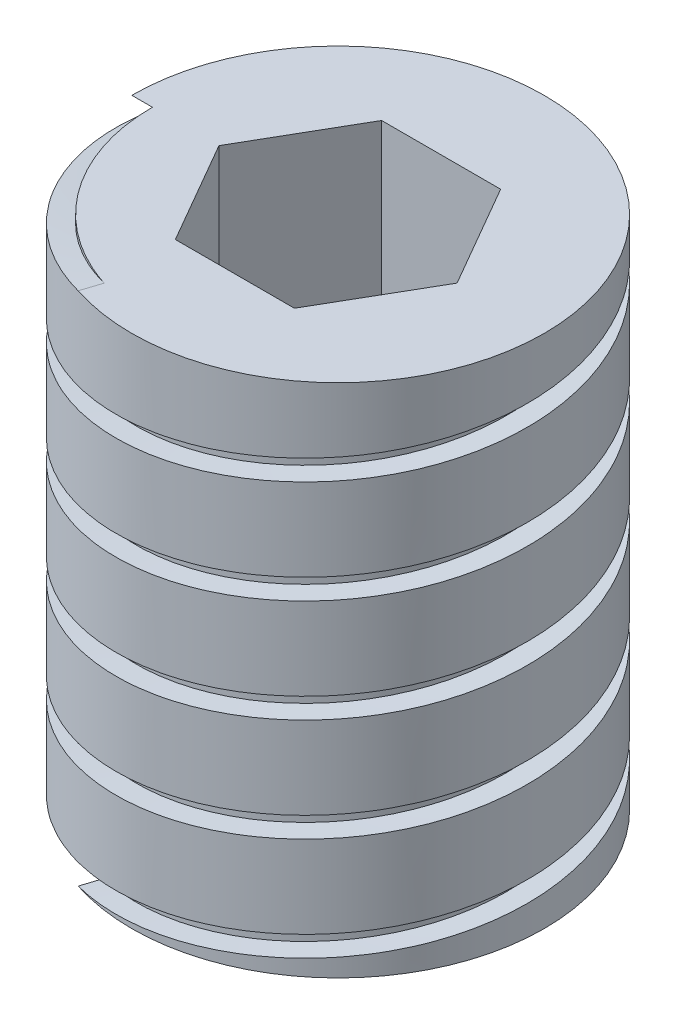
SolidWorks part; units mm, degrees
material "Plain Carbon Steel"
ref_plane "Front Plane" through (0, 0, 0) normal (0, 0, 1) x (1, 0, 0)
ref_plane "Top Plane" through (0, 0, 0) normal (0, 1, 0) x (1, 0, 0)
ref_plane "Right Plane" through (0, 0, 0) normal (1, 0, 0) x (0, 0, -1)
sketch "Sketch1" plane through (0, 0, 0) normal (0, 1, 0) x (1, 0, 0)
  circle A0 centre (0, 0) radius 40
  dimension "D1" = 80
extrude "Boss-Extrude1" add sketch "Sketch1" against normal blind 100
sketch "Sketch2" plane through (0, 0, 0) normal (0, 1, 0) x (1, 0, 0)
  line L0 (-23.094, 0) -> (23.094, 0) construction
  line L2 (23.094, 0) -> (11.547, 20)
  line L3 (11.547, 20) -> (-11.547, 20)
  line L4 (-11.547, 20) -> (-23.094, 0)
  line L5 (-23.094, 0) -> (-11.547, -20)
  line L6 (-11.547, -20) -> (11.547, -20)
  line L7 (11.547, -20) -> (23.094, 0)
  circle A0 centre (0, 0) radius 20 construction
  point P4 (0, 0)
  dimension "D1" = 40
extrude "Cut-Extrude1" cut sketch "Sketch2" against normal blind 100
sketch "Sketch3" plane through (0, 0, 0) normal (0, 1, 0) x (1, 0, 0)
  circle A2 centre (0, 0) radius 40
  circle A3 centre (0, 0) radius 40
  dimension "D1" = 0
sketch "Sketch4" plane through (0, 0, 0) normal (0, 1, 0) x (1, 0, 0)
  circle A0 centre (0, 0) radius 40 construction
  circle A1 centre (0, 0) radius 40
curve "Helix/Spiral2" pitch 20 height 100 turns 5
sketch "Sketch5" plane through (0, 0, 0) normal (0, 0, 1) x (1, 0, 0)
  line L1 (-40, -100) -> (-36, -100)
  line L2 (-40, -100) -> (-40, -104)
  line L3 (-40, -104) -> (-36, -104)
  line L4 (-36, -100) -> (-36, -104)
  dimension "D1" = 4
  dimension "D2" = 4
sweep "Cut-Sweep2" cut profiles "Sketch5" path "Helix/Spiral2" align with end faces yes
